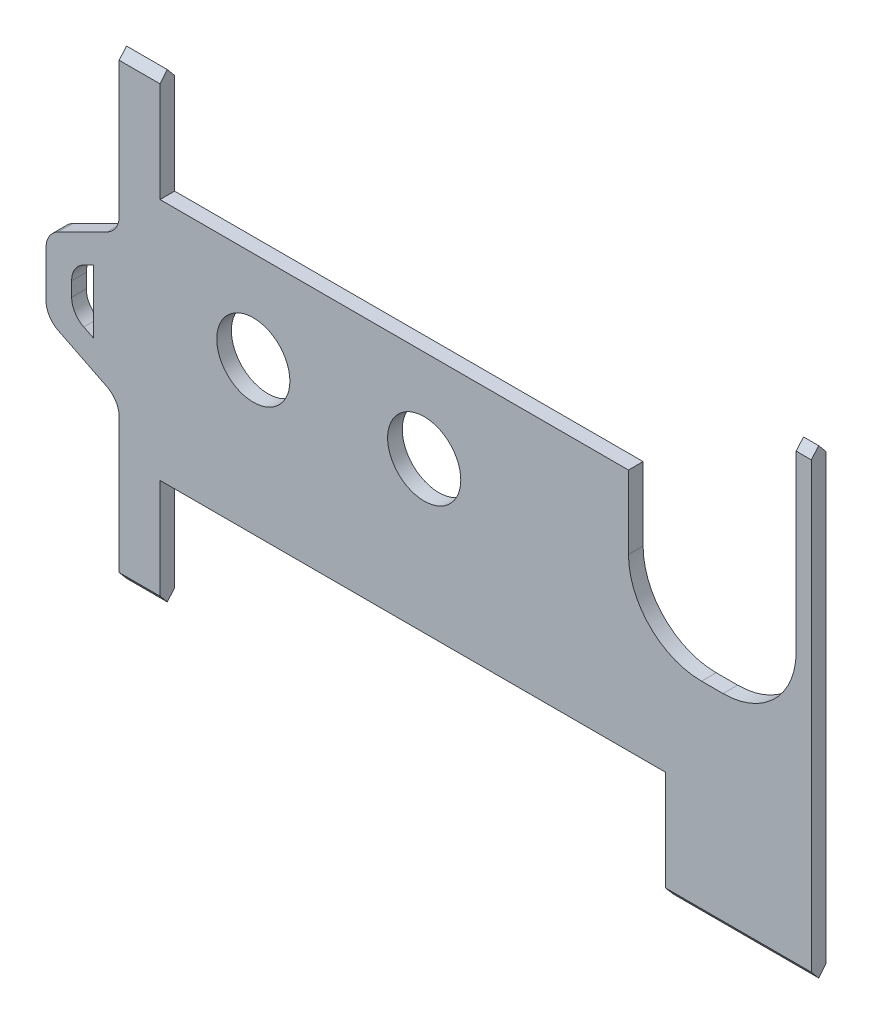
SolidWorks part; units mm, degrees
ref_plane "Front Plane" through (0, 0, 0) normal (0, 0, 1) x (1, 0, 0)
ref_plane "Top Plane" through (0, 0, 0) normal (0, 1, 0) x (1, 0, 0)
ref_plane "Right Plane" through (0, 0, 0) normal (1, 0, 0) x (0, 0, -1)
sketch "Sketch1" plane through (0, 0, 11.1483) normal (0, 0, 1) x (1, 0, 0)
  line L0 (22.423, 106.8975) -> (12.423, 101.8975)
  line L5 (22.223, 125.272) -> (22.223, 68.523) construction
  line L10 (12.423, 101.8975) -> (12.423, 91.8975)
  line L11 (117.248, 128.723) -> (22.223, 128.723) construction
  line L12 (117.248, 128.723) -> (117.248, 65.072) construction
  line L13 (117.248, 65.072) -> (22.223, 65.072) construction
  line L14 (22.223, 128.723) -> (22.223, 65.072) construction
  line L15 (117.048, 128.523) -> (22.423, 128.523)
  line L16 (22.423, 128.523) -> (22.423, 65.272)
  line L17 (117.048, 65.272) -> (22.423, 65.272)
  line L18 (117.048, 128.523) -> (117.048, 65.272)
  line L19 (12.423, 91.8975) -> (22.423, 86.8975)
  line L20 (92.048, 128.523) -> (92.048, 93.523)
  line L21 (92.048, 93.523) -> (117.048, 93.523)
  line L22 (114.9758, 128.523) -> (114.9758, 93.523)
  line L25 (22.423, 106.8975) -> (22.423, 86.8975)
  line L26 (15.923, 94.0606) -> (18.923, 92.5606)
  line L27 (18.923, 101.2344) -> (18.923, 92.5606)
  line L28 (18.923, 101.2344) -> (15.923, 99.7344)
  line L29 (15.923, 99.7344) -> (15.923, 94.0606)
  line L30 (-882.952, 96.8975) -> (49117.048, 96.8975) construction
  line L31 (28.0044, 130.223) -> (28.0044, 127.223) construction
  line L32 (28.0044, 128.523) -> (97.1229, 128.523)
  line L33 (28.0044, 128.523) -> (28.0044, 113.523)
  line L34 (28.0044, 113.523) -> (97.1229, 113.523)
  line L35 (97.1229, 128.523) -> (97.1229, 113.523)
  line L37 (97.1229, 130.223) -> (97.1229, 127.223) construction
  line L38 (28.0044, 80.272) -> (97.1229, 80.272)
  line L39 (97.1229, 65.272) -> (97.1229, 80.272)
  line L40 (28.0044, 65.272) -> (97.1229, 65.272)
  line L41 (28.0044, 65.272) -> (28.0044, 80.272)
  circle A0 centre (40.7588, 100.907) radius 5
  circle A1 centre (64.1228, 100.8815) radius 5
  point P4 (22.423, 96.8975)
  point P8 (12.423, 96.8975)
  point P34 (117.048, 96.8975)
  dimension "D7" = 10
  dimension "D8" = 10
  dimension "D1" = 0.2
  dimension "D2" = 10
  dimension "D3" = 10
  dimension "D4" = 20
  dimension "D5" = 35
  dimension "D6" = 25
  dimension "D9" = 3.5
  dimension "D10" = 15
  dimension "D11" = 6.5
extrude "Boss-Extrude1" add sketch "Sketch1" along normal mid plane 2 contours L18 L15 L16 L17 | L10 L19 L16 L0 | L15 L22 L21 L18 region at (22.1994, 96.8975, 11.1483) region at (66.0201, 93.1246, 11.1483) region at (116.0119, 111.023, 11.1483)
sketch "Sketch2" plane through (22.423, 0, 0) normal (-1, 0, 0) x (0, 0, 1)
  line L5 (-986.1517, 96.8975) -> (49013.8483, 96.8975) construction
  line L6 (13.8483, 68.523) -> (13.8483, 125.272) construction
  line L7 (10.1013, 128.523) -> (10.1013, 127.1682)
  line L8 (12.1953, 127.1682) -> (11.1483, 128.4124)
  line L10 (12.1953, 66.6268) -> (12.1953, 65.272)
  line L11 (12.1953, 65.272) -> (10.1013, 65.272)
  line L12 (11.1483, 65.3826) -> (10.1013, 66.6268)
  line L13 (12.1953, 66.6268) -> (11.1483, 65.3826)
  line L14 (11.1483, 65.3826) -> (10.1013, 66.6268)
  line L15 (12.1953, 66.6268) -> (11.1483, 65.3826)
  line L16 (10.1013, 65.272) -> (10.1013, 66.6268)
  line L17 (12.1483, 65.272) -> (10.1483, 65.272) construction
  line L18 (11.1483, 128.4124) -> (10.1013, 127.1682)
  line L19 (12.1953, 128.523) -> (10.1013, 128.523)
  line L20 (12.1953, 127.1682) -> (12.1953, 128.523)
  point P9 (13.8483, 96.8975)
  dimension "D2" = 0.2
extrude "Cut-Extrude1" cut sketch "Sketch2" against normal through all
fillet "Fillet1" radius 10 2 edges at (92.048, 93.523, 11.1483) (114.9758, 93.523, 11.1483)
fillet "Fillet2" radius 3 6 edges at (15.923, 99.7344, 11.1483) (15.923, 94.0606, 11.1483) (22.423, 106.8975, 11.1483) (12.423, 101.8975, 11.1483) (12.423, 91.8975, 11.1483) (22.423, 86.8975, 11.1483)
